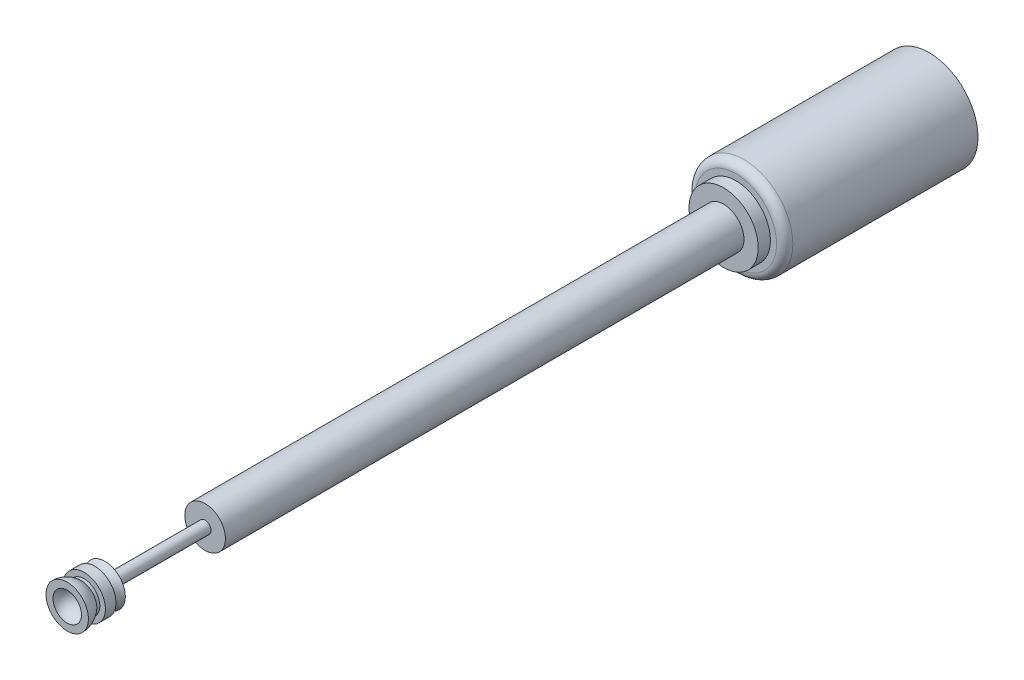
SolidWorks part; units mm, degrees
ref_plane "Front Plane" through (0, 0, 0) normal (0, 0, 1) x (1, 0, 0)
ref_plane "Top Plane" through (0, 0, 0) normal (0, 1, 0) x (1, 0, 0)
ref_plane "Right Plane" through (0, 0, 0) normal (1, 0, 0) x (0, 0, -1)
sketch "Sketch1" plane through (0, 0, 0) normal (0, 0, 1) x (1, 0, 0)
  circle A0 centre (0, 0) radius 0.5
  circle A1 centre (0, 0) radius 1.2
  dimension "D1" = 2.4
  dimension "D2" = 1
extrude "Boss-Extrude1" add sketch "Sketch1" along normal blind 15.5 contours A0 region at (0, 0, 0)
extrude "Boss-Extrude2" add sketch "Sketch1<3>" against normal blind 4.75 separate body contours A1 A0 | A0 region at (-1.1661, 0, 0)
sketch "Sketch1<3>" plane through (0, 0, 0) normal (0, 0, 1) x (1, 0, 0) same geometry as "Sketch1"
fillet "Fillet1" radius 0.2 1 edges at (1.2, 0, 0)
sketch "Sketch3" plane through (0, 0, 0) normal (0, 1, 0) x (1, 0, 0)
  line L0 (0.5, -15.5) -> (0, -15.5)
  line L1 (-0.5, -15.5) -> (0.5, -15.5) construction
  line L2 (0, -15.5) -> (0, -16.0775)
  line L3 (0.35, -16.4275) -> (0.5212, -16.4275)
  line L4 (0.3844, -16.0839) -> (0.3844, -16.0106)
  line L5 (0.3844, -16.0106) -> (0.5212, -16.0106)
  line L6 (0.5212, -16.0106) -> (0.5212, -15.7498)
  line L7 (0.5212, -15.7498) -> (0.4082, -15.7498)
  arc A0 (0, -16.0775) -> (0.35, -16.4275) centre (0, -16.4275) cw
  arc A1 (0.5212, -16.4275) -> (0.3844, -16.0839) centre (0.0212, -16.4275) ccw
  arc A2 (0.4082, -15.7498) -> (0.5, -15.5) centre (0.7941, -15.7498) cw
  dimension "D2" = 0.35
  dimension "D3" = 0.5
  dimension "D1" = 0.9275
revolve "Revolve1" add sketch "Sketch3" angle 360 about L2
sketch "Sketch8" plane through (0, 0, 0) normal (0, 1, 0) x (1, 0, 0)
  line L0 (0.5, -15.5) -> (-0.5, -15.5) construction
  line L1 (-0.1481, -15.5) -> (-0.9321, -15.5)
  line L2 (-0.1481, -15.5) -> (-0.1481, -13.04)
  line L3 (-0.1481, -13.04) -> (-0.9321, -13.04)
  line L4 (-0.9321, -15.5) -> (-0.9321, -13.04)
  line L5 (0, -15.5) -> (0, -16.4646) construction
  dimension "D1" = 0.2962
  dimension "D2" = 2.46
revolve "Cut-Revolve2" cut sketch "Sketch8" angle 360 about L5
sketch "Sketch9" plane through (0, 0, 0) normal (0, 0, 1) x (1, 0, 0)
  circle A0 centre (0, 0) radius 0.85
  dimension "D1" = 1.7
extrude "Boss-Extrude5" add sketch "Sketch9" along normal blind 0.3
sketch "Sketch10" plane through (0, 0, -4.75) normal (0, 0, -1) x (-1, 0, 0)
  point P0 (0, 0)
